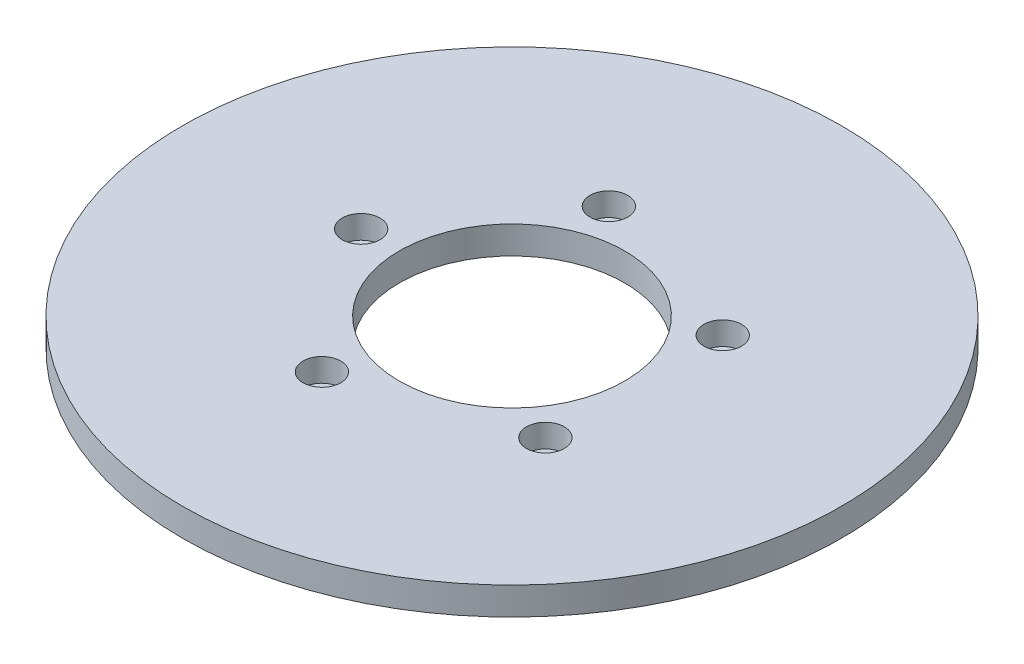
SolidWorks part; units mm, degrees
ref_plane "Front Plane" through (0, 0, 0) normal (0, 0, 1) x (1, 0, 0)
ref_plane "Top Plane" through (0, 0, 0) normal (0, 1, 0) x (1, 0, 0)
ref_plane "Right Plane" through (0, 0, 0) normal (1, 0, 0) x (0, 0, -1)
sketch "Sketch1" plane through (0, 0, 0) normal (0, 1, 0) x (1, 0, 0)
  circle A0 centre (0, 0) radius 95
  dimension "FLANGE_OD" = 190
extrude "Boss-Extrude1" add sketch "Sketch1" along normal blind 8
sketch "Sketch2" plane through (0, 0, 0) normal (0, 1, 0) x (1, 0, 0)
  circle A0 centre (0, 0) radius 32.5
  dimension "BORE_D" = 65
extrude "Cut-Extrude1" cut sketch "Sketch2" along normal through all
sketch "Sketch3" plane through (0, 8, 0) normal (0, 1, 0) x (1, 0, 0)
  circle A0 centre (0, 0) radius 43.4884 construction
  circle A1 centre (-43.4884, 0) radius 5.4401
  dimension "BOLT_D" = 10.8803
  dimension "BOLT_PCD" = 86.9768
extrude "Cut-Extrude2" cut sketch "Sketch3" against normal blind 6.6757
pattern_circular "CirPattern1" count 5 over 360 about axis through (0, 0, 0) along (0, 1, 0) of "Cut-Extrude2"
